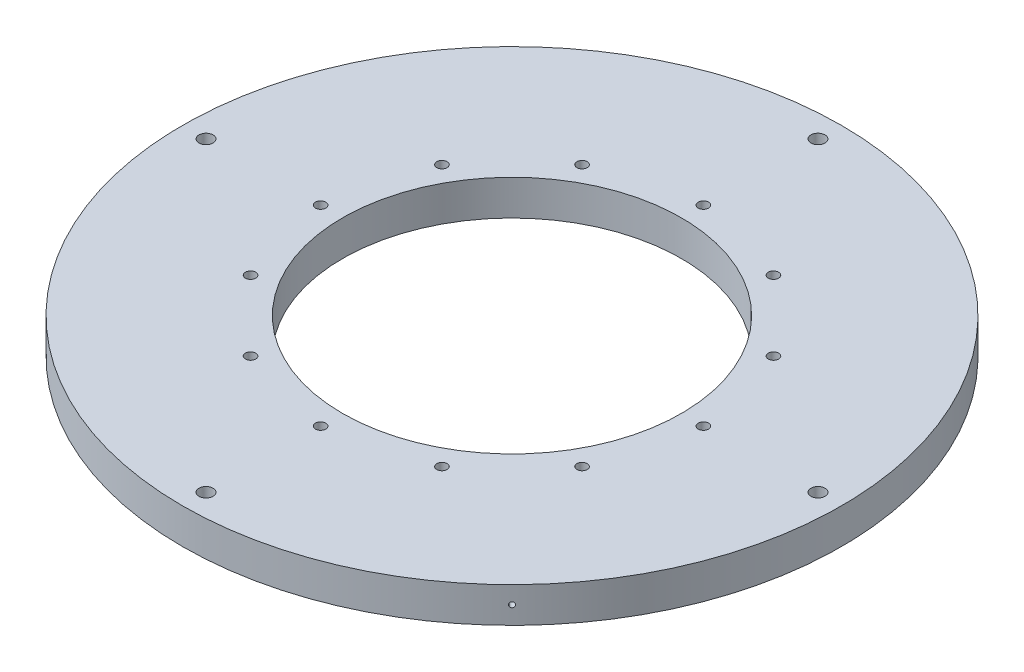
SolidWorks part; units mm, degrees
material "6061-T6 (SS)"
ref_plane "Front Plane" through (0, 0, 0) normal (0, 0, 1) x (1, 0, 0)
ref_plane "Top Plane" through (0, 0, 0) normal (0, 1, 0) x (1, 0, 0)
ref_plane "Right Plane" through (0, 0, 0) normal (1, 0, 0) x (0, 0, -1)
sketch "Sketch1" plane through (0, 0, 0) normal (0, 1, 0) x (1, 0, 0)
  circle A0 centre (0, 0) radius 88.9
  dimension "D1" = 177.8
extrude "Boss-Extrude1" add sketch "Sketch1" along normal blind 9.525
sketch "Sketch2" plane through (0, 9.525, 0) normal (0, 1, 0) x (1, 0, 0)
  circle A0 centre (0, 0) radius 45.72
extrude "Cut-Extrude1" cut sketch "Sketch2" against normal blind 12.7
sketch "Sketch3" plane through (0, 9.525, 0) normal (0, 1, 0) x (1, 0, 0)
  line L0 (0, 0) -> (0, 131.3286) construction
  circle A0 centre (0, 51.6382) radius 1.397
  point P0 (0, 51.6382)
  dimension "D2" = 2.794
  dimension "D1" = 51.6382
extrude "Cut-Extrude2" cut sketch "Sketch3" against normal blind 12.7
pattern_circular "CirPattern1" count 12 over 360 about axis through (0, 9.525, 0) along (0, 1, 0) of "Cut-Extrude2"
sketch "Sketch4" plane through (0, 9.525, 0) normal (0, 1, 0) x (1, 0, 0)
  line L0 (0, 0) -> (0, 115.2639) construction
  circle A0 centre (0, 82.55) radius 1.905
  dimension "D1" = 3.81
  dimension "D2" = 82.55
extrude "Cut-Extrude3" cut sketch "Sketch4" against normal blind 12.7
pattern_circular "CirPattern2" count 4 over 360 about axis through (0, 9.525, 0) along (0, 1, 0) of "Cut-Extrude3"
ref_plane "Plane3" through (-62.8618, 0, -62.8618) normal (-0.7071, 0, -0.7071) x (0, -1, 0)
sketch "Sketch10" plane through (-62.8618, 0, -62.8618) normal (-0.7071, 0, -0.7071) x (0, -1, 0)
  line L0 (0, 0) -> (-9.652, 0) construction
  circle A1 centre (-4.826, 0) radius 0.6985
  dimension "D2" = 1.397
  dimension "D1" = 9.652
extrude "Cut-Extrude5" cut sketch "Sketch10" against normal blind 3.175
pattern_circular "CirPattern5" count 4 over 360 about axis through (0, 9.525, 0) along (0, 1, 0) of "Cut-Extrude5"
